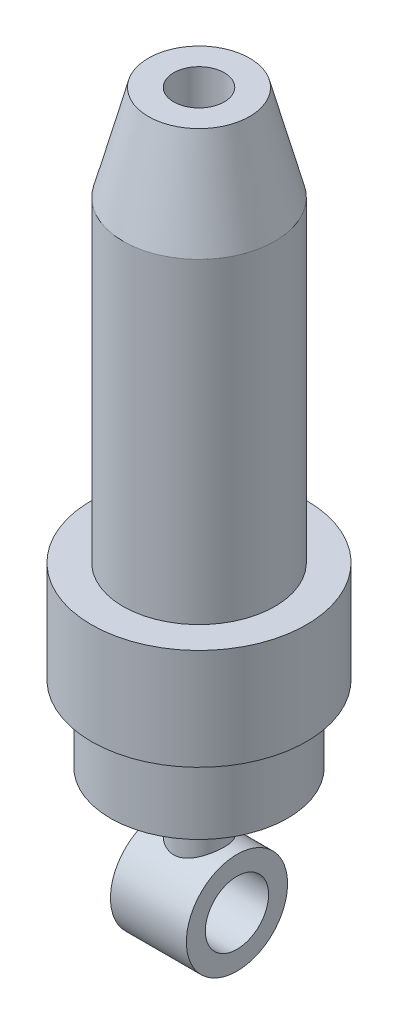
SolidWorks part; units mm, degrees
ref_plane "前视基准面" through (0, 0, 0) normal (0, 0, 1) x (1, 0, 0)
ref_plane "上视基准面" through (0, 0, 0) normal (0, 1, 0) x (1, 0, 0)
ref_plane "右视基准面" through (0, 0, 0) normal (1, 0, 0) x (0, 0, -1)
sketch "草图1" plane through (0, 0, 0) normal (1, 0, 0) x (0, 0, -1)
  line L0 (0, 20) -> (0, -65) construction
  circle A0 centre (0, 20) radius 1.5
  circle A1 centre (0, 20) radius 4.5
  circle A2 centre (0, -65) radius 2.5
  circle A3 centre (0, -65) radius 4
  dimension "D1" = 3
  dimension "D2" = 9
  dimension "D3" = 20
  dimension "D5" = 5
  dimension "D6" = 8
  dimension "D4" = 85
extrude "凸台-拉伸1" add sketch "草图1" along normal blind 3 and the other way blind 3
sketch "草图2" plane through (0, 0, 0) normal (0, 1, 0) x (1, 0, 0)
  circle A0 centre (0, 0) radius 3
  dimension "D1" = 6
extrude "凸台-拉伸2" add sketch "草图2" along normal up to surface (16.6459 mm away) up to face at (-3, 20, -4.5)
sketch "草图3" plane through (0, 0, 0) normal (0, -1, 0) x (1, 0, 0)
  circle A0 centre (0, 0) radius 3
  dimension "D1" = 6
extrude "切除-拉伸1" cut sketch "草图3" against normal blind 10
sketch "草图4" plane through (0, 10, 0) normal (0, -1, 0) x (1, 0, 0)
  circle A0 centre (0, 0) radius 2
  dimension "D1" = 4
extrude "凸台-拉伸3" add sketch "草图4" along normal blind 20
sketch "草图5" plane through (0, 0, 0) normal (1, 0, 0) x (0, 0, -1)
  line L0 (0, -10) -> (4, -10)
  line L1 (4, -10) -> (6, -17.5359)
  line L2 (6, -17.5359) -> (6, -42.5359)
  line L3 (6, -42.5359) -> (8.5, -42.5359)
  line L4 (8.5, -42.5359) -> (8.5, -50.5359)
  line L5 (8.5, -50.5359) -> (7, -50.5359)
  line L6 (7, -50.5359) -> (7, -56.5359)
  line L7 (7, -56.5359) -> (2, -56.5359)
  line L8 (-2, -10) -> (2, -10) construction
  line L9 (0, -10) -> (0, -61) construction
  line L10 (2, -56.5359) -> (2, -61.5359)
  line L11 (2, -61.5359) -> (0, -61)
  line L12 (0, -61) -> (0, -10)
  circle A0 centre (0, -65) radius 4 construction
  dimension "D1" = 4
  dimension "D2" = 6
  dimension "D3" = 25
  dimension "D4" = 8
  dimension "D5" = 6
  dimension "D6" = 5
  dimension "D7" = 8.5
  dimension "D8" = 7
  dimension "D9" = 2
revolve "旋转2" add sketch "草图5" angle 360 about L9
sketch "草图6" plane through (0, 0, 0) normal (1, 0, 0) x (0, 0, -1)
  line L0 (4, -10) -> (-4, -10)
  line L1 (-4, -10) -> (-9.6323, 30.289)
  line L2 (-9.6323, 30.289) -> (12.2666, 30.289)
  line L3 (12.2666, 30.289) -> (4, -10)
extrude "切除-拉伸2" cut sketch "草图6" against normal blind 20 and the other way blind 20
sketch "草图7" plane through (0, -10, 0) normal (0, 1, 0) x (1, 0, 0)
  circle A0 centre (0, 0) radius 2
  dimension "D1" = 4
extrude "切除-拉伸3" cut sketch "草图7" against normal blind 30
